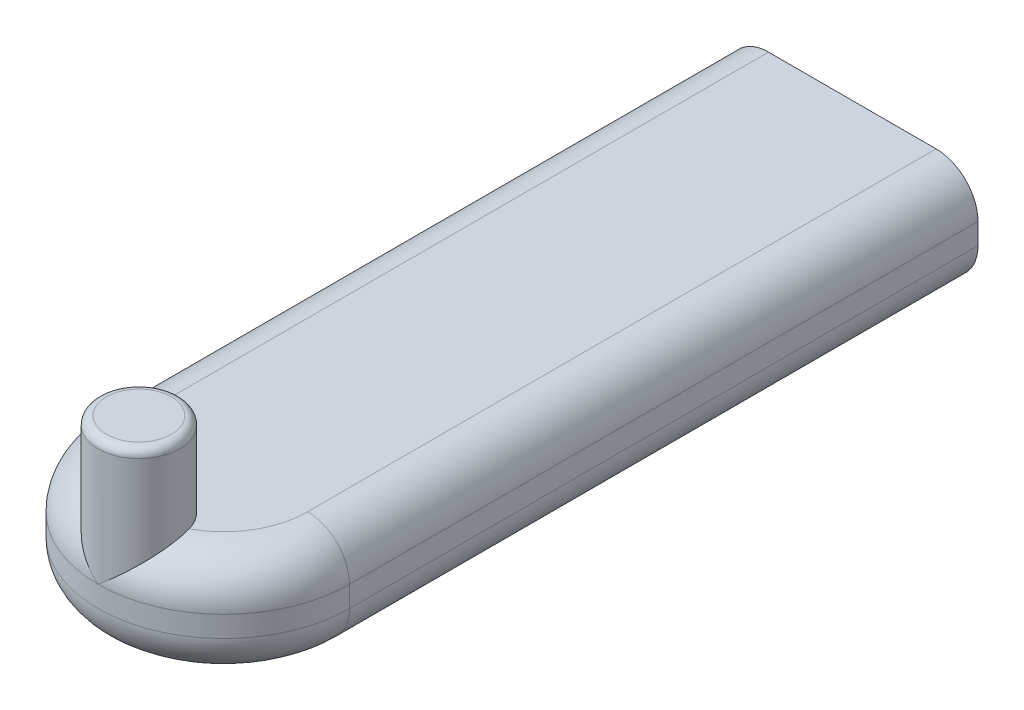
SolidWorks part; units mm, degrees
ref_plane "Front Plane" through (0, 0, 0) normal (0, 0, 1) x (1, 0, 0)
ref_plane "Top Plane" through (0, 0, 0) normal (0, 1, 0) x (1, 0, 0)
ref_plane "Right Plane" through (0, 0, 0) normal (1, 0, 0) x (0, 0, -1)
sketch "Sketch1" plane through (0, 0, 0) normal (0, 1, 0) x (1, 0, 0)
  line L0 (-6, 0) -> (-6, 30)
  line L1 (0, 6) -> (0, 30) construction
  line L2 (-6, 30) -> (6, 30)
  line L3 (6, 0) -> (6, 30)
  circle A0 centre (0, 0) radius 3 construction
  arc A1 (-6, 0) -> (6, 0) centre (0, 0) ccw
  dimension "D1" = 3
  dimension "D2" = 6
  dimension "D3" = 30
extrude "Boss-Extrude1" add sketch "Sketch1" along normal blind 5
sketch "Sketch2" plane through (0, 0, -30) normal (0, 0, -1) x (-1, 0, 0)
  line L0 (0, 5) -> (0, 0) construction
  line L1 (-6, 5) -> (6, 5) construction
  circle A0 centre (0, 2.5) radius 1.95
  dimension "D1" = 1.95
extrude "Cut-Extrude1" cut sketch "Sketch2" against normal blind 8
sketch "Sketch3" plane through (0, 5, 0) normal (0, 1, 0) x (1, 0, 0)
  circle A0 centre (0, 0) radius 1.95 construction
  circle A2 centre (0, -4.05) radius 1.95
  arc A3 (-6, 0) -> (6, 0) centre (0, 0) ccw construction
  point P9 (0, -6)
  dimension "D1" = 1.95
extrude "Boss-Extrude2" add sketch "Sketch3" along normal blind 4
fillet "Fillet2" radius 2 7 edges at (0, 0, 6) (-4.2426, 5, 4.2426) (4.2426, 5, 4.2426) (-6, 5, -15) (-6, 0, -15) (6, 0, -15) (6, 5, -15)
fillet "Fillet3" radius 0.4 1 edges at (0, 9, 6)
